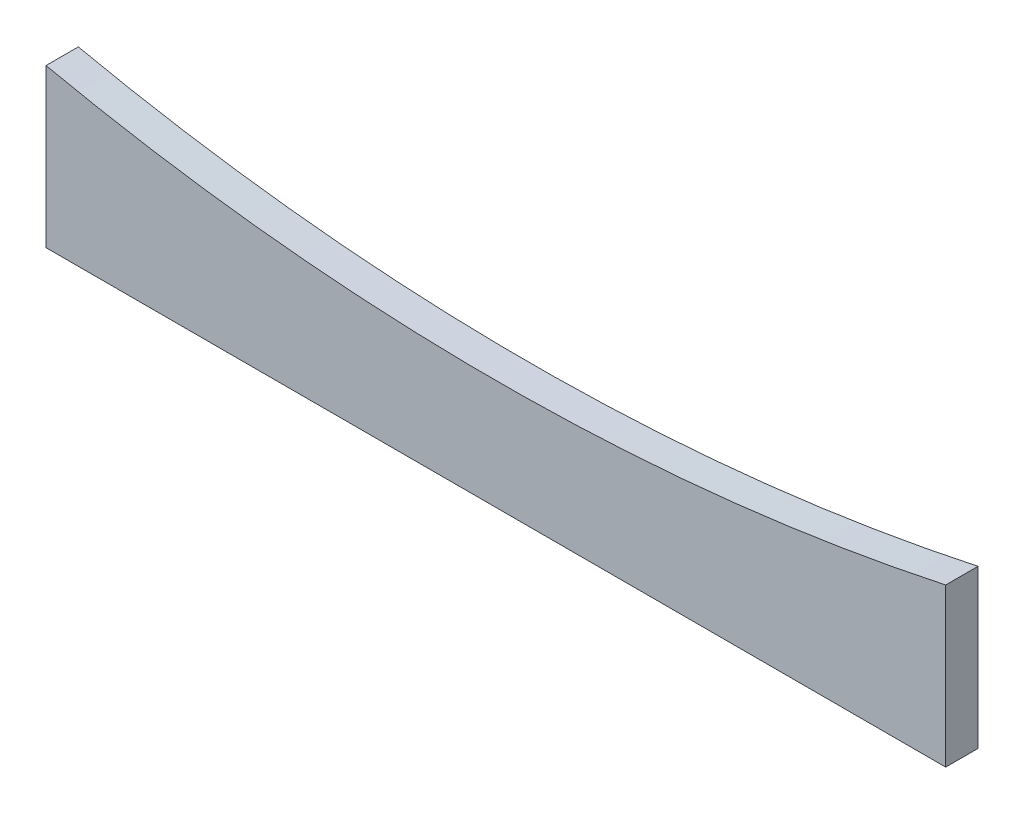
SolidWorks part; units mm, degrees
ref_plane "Alzado" through (0, 0, 0) normal (0, 0, 1) x (1, 0, 0)
ref_plane "Planta" through (0, 0, 0) normal (0, 1, 0) x (1, 0, 0)
ref_plane "Vista lateral" through (0, 0, 0) normal (1, 0, 0) x (0, 0, -1)
sketch "Croquis1" plane through (0, 0, 0) normal (0, 0, 1) x (1, 0, 0)
  line L0 (-54.6778, 18.6615) -> (-54.6778, -12.3385)
  line L1 (-54.6778, -12.3385) -> (122.1222, -12.3385)
  line L2 (122.1222, -12.3385) -> (122.1222, 18.6615)
  line L3 (33.7222, 429.2531) -> (33.7222, -12.3385) construction
  arc A0 (-54.6778, 18.6615) -> (122.1222, 18.6615) centre (33.7222, 429.2531) ccw
  dimension "D3" = 420
  dimension "D1" = 31
  dimension "D2" = 176.8
base flange "Brida base1" sketch "Croquis1" thickness 6.35 reverse thickness direction no parameters "D1"=0.7366
sketch "Líneas de pliegue1" [suppressed] plane through (0, 0, 0) normal (0, 1, 0) x (1, 0, 0)
sketch "Cuadro delimitador1" [suppressed] plane through (0, 0, 0) normal (0, 1, 0) x (1, 0, 0)
sheet metal parameters "Chapa metálica1" thickness 6.35 parameters "D1"=0.7366
flat pattern "Chapa desplegada1" [suppressed]
sketch "Líneas de pliegue2" plane through (0, 0, 0) normal (0, 1, 0) x (1, 0, 0)
sketch3d "Cuadro delimitador2" [suppressed]
  line L0 (-88.4, -441.5916, 0) -> (88.4, -441.5916, 0) construction
  line L1 (-88.4, -410.5916, 0) -> (88.4, -410.5916, 0) construction
  line L2 (-88.4, -441.5916, 0) -> (-88.4, -410.5916, 0) construction
  line L3 (88.4, -441.5916, 0) -> (88.4, -410.5916, 0) construction
